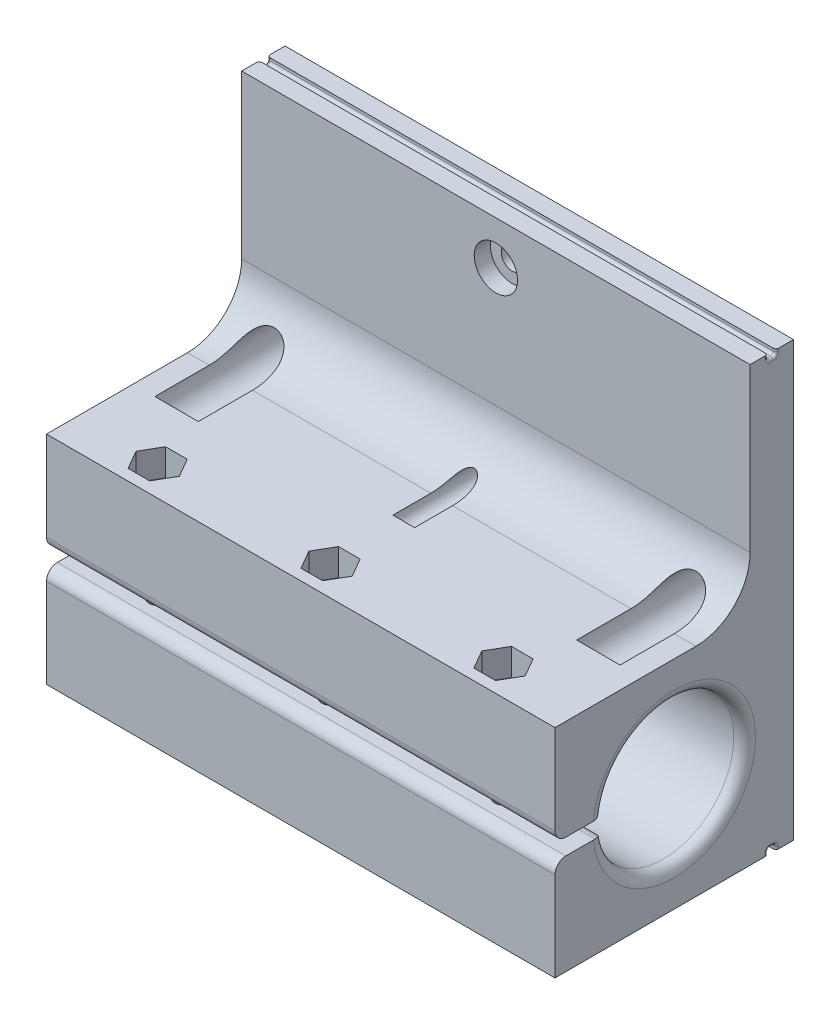
SolidWorks part; units mm, degrees
ref_plane "Front Plane" through (0, 0, 0) normal (0, 0, 1) x (1, 0, 0)
ref_plane "Top Plane" through (0, 0, 0) normal (0, 1, 0) x (1, 0, 0)
ref_plane "Right Plane" through (0, 0, 0) normal (1, 0, 0) x (0, 0, -1)
sketch "Sketch1" plane through (0, 0, 0) normal (0, 0, 1) x (1, 0, 0)
  line L1 (-46.9, -40) -> (46.9, -40)
  line L2 (-46.9, -40) -> (-46.9, 40)
  line L3 (-46.9, 40) -> (46.9, 40)
  line L4 (46.9, -40) -> (46.9, 40)
  line L5 (-46.9, -40) -> (46.9, 40) construction
  line L6 (-46.9, 40) -> (46.9, -40) construction
  point P0 (0, 0)
  dimension "D1" = 93.8
  dimension "D2" = 80
extrude "Boss-Extrude1" add sketch "Sketch1" along normal blind 8
sketch "Sketch4" plane through (0, 0, 0) normal (0, 0, -1) x (-1, 0, 0)
  circle A0 centre (0, -32) radius 2
  circle A1 centre (0, 32) radius 2
  circle A2 centre (38.9, 0) radius 2
  circle A3 centre (-38.9, 0) radius 2
extrude "Cut-Extrude2" cut sketch "Sketch4" against normal through all
sketch "Sketch5" plane through (0, 0, 0) normal (0, 0, -1) x (-1, 0, 0)
  line L1 (0, 4.001) -> (-3.465, 2.0005)
  line L2 (-3.465, 2.0005) -> (-3.465, -2.0005)
  line L3 (-3.465, -2.0005) -> (0, -4.001)
  line L4 (0, -4.001) -> (3.465, -2.0005)
  line L5 (3.465, -2.0005) -> (3.465, 2.0005)
  line L6 (3.465, 2.0005) -> (0, 4.001)
  circle A0 centre (0, 0) radius 3.465 construction
  dimension "D1" = 6.93
extrude "Cut-Extrude3" cut sketch "Sketch5" against normal blind 5
sketch "Sketch9" plane through (0, 0, 8) normal (0, 0, 1) x (1, 0, 0)
  line L0 (46.9, -40) -> (46.9, 40) construction
  line L1 (-46.9, -40) -> (46.9, -40)
  line L2 (-46.9, -40) -> (-46.9, 0)
  line L3 (-46.9, 0) -> (46.9, 0)
  line L4 (46.9, -40) -> (46.9, 0)
  dimension "D1" = 40
extrude "Boss-Extrude2" add sketch "Sketch9" along normal blind 36
sketch "Sketch8" plane through (0, 0, 8) normal (0, 0, 1) x (1, 0, 0)
  circle A0 centre (0, 32) radius 4
  circle A3 centre (-38.9, 0) radius 4
  circle A4 centre (38.9, 0) radius 4
  dimension "D1" = 8
  dimension "D2" = 8
  dimension "D3" = 8
extrude "Cut-Extrude5" cut sketch "Sketch8" against normal blind 3 and the other way blind 20
sketch "Sketch7" plane through (0, 0, 5) normal (0, 0, -1) x (-1, 0, 0)
  circle A0 centre (0, 0) radius 2
extrude "Cut-Extrude4" cut sketch "Sketch7" against normal blind 20
fillet "Fillet1" radius 10 1 edges at (-18.45, 0, 8)
sketch "Sketch10" plane through (-46.9, 0, 0) normal (-1, 0, 0) x (0, 0, 1)
  line L0 (44, -20) -> (0, -20) construction
  line L1 (44, 0) -> (44, -40) construction
  line L2 (0, 40) -> (0, -40) construction
  line L4 (34.9132, -18.5) -> (44, -18.5)
  line L6 (34.9132, -21.5) -> (44, -21.5)
  line L7 (44, -18.5) -> (44, -21.5)
  arc A0 (34.9132, -18.5) -> (34.9132, -21.5) centre (22, -20) ccw
  dimension "D2" = 26
  dimension "D1" = 22
  dimension "D3" = 1.5
  dimension "D4" = 3
extrude "Cut-Extrude6" cut sketch "Sketch10" against normal through all
fillet "Fillet2" radius 2 6 edges at (46.9, -20, 9) (-46.9, -20, 9) (0, -21.5, 44) (0, -21.5, 34.9132) (0, -18.5, 44) (0, -18.5, 34.9132)
sketch "Sketch11" plane through (0, -40, 0) normal (0, -1, 0) x (1, 0, 0)
  line L0 (-46.9, 38.5) -> (46.9, 38.5) construction
  line L1 (-46.9, 44) -> (-46.9, 0) construction
  line L2 (46.9, 44) -> (46.9, 0) construction
  line L3 (-46.9, 44) -> (46.9, 44) construction
  line L4 (0, 38.5) -> (0, 28.0799) construction
  circle A0 centre (-31.9, 38.5) radius 1.6
  circle A1 centre (0, 38.5) radius 1.6
  circle A3 centre (31.9, 38.5) radius 1.6
  dimension "D3" = 3.2
  dimension "D1" = 5.5
  dimension "D2" = 15
extrude "Cut-Extrude7" cut sketch "Sketch11" against normal through all
sketch "Sketch12" plane through (0, 0, 0) normal (0, 1, 0) x (1, 0, 0)
  line L0 (46.9, -44) -> (-46.9, -44) construction
  line L1 (-27.9047, -38.5) -> (-29.9024, -35.04)
  line L2 (-29.9024, -35.04) -> (-33.8976, -35.04)
  line L3 (-33.8976, -35.04) -> (-35.8953, -38.5)
  line L4 (-35.8953, -38.5) -> (-33.8976, -41.96)
  line L5 (-33.8976, -41.96) -> (-29.9024, -41.96)
  line L6 (-29.9024, -41.96) -> (-27.9047, -38.5)
  line L7 (3.9953, -38.5) -> (1.9976, -35.04)
  line L8 (1.9976, -35.04) -> (-1.9976, -35.04)
  line L9 (-1.9976, -35.04) -> (-3.9953, -38.5)
  line L10 (-3.9953, -38.5) -> (-1.9976, -41.96)
  line L11 (-1.9976, -41.96) -> (1.9976, -41.96)
  line L12 (1.9976, -41.96) -> (3.9953, -38.5)
  line L13 (35.8953, -38.5) -> (33.8976, -35.04)
  line L14 (33.8976, -35.04) -> (29.9024, -35.04)
  line L15 (29.9024, -35.04) -> (27.9047, -38.5)
  line L16 (27.9047, -38.5) -> (29.9024, -41.96)
  line L17 (29.9024, -41.96) -> (33.8976, -41.96)
  line L18 (33.8976, -41.96) -> (35.8953, -38.5)
  circle A0 centre (-31.9, -38.5) radius 3.46 construction
  circle A1 centre (0, -38.5) radius 3.46 construction
  circle A2 centre (31.9, -38.5) radius 3.46 construction
  dimension "D1" = 6.92
extrude "Cut-Extrude8" cut sketch "Sketch12" against normal blind 5
sketch "Sketch13" plane through (0, -40, 0) normal (0, -1, 0) x (1, 0, 0)
  circle A0 centre (-31.9, 38.5) radius 4.5
  circle A1 centre (0, 38.5) radius 4.5
  circle A2 centre (31.9, 38.5) radius 4.5
  dimension "D1" = 9
extrude "Cut-Extrude9" cut sketch "Sketch13" against normal blind 3
sketch "Sketch14" plane through (0, -40, 0) normal (0, -1, 0) x (1, 0, 0)
  line L0 (0, 0) -> (0, 29.1114) construction
  line L1 (-46.9, 0) -> (46.9, 0) construction
  line L2 (-4, 13) -> (4, 13)
  line L3 (-4, 13) -> (-4, 8)
  line L4 (-4, 8) -> (4, 8)
  line L5 (4, 13) -> (4, 8)
  dimension "D1" = 8
  dimension "D2" = 4
  dimension "D3" = 8
  dimension "D4" = 5
extrude "Cut-Extrude10" cut sketch "Sketch14" against normal blind 15
sketch "Sketch15" plane through (0, 0, 13) normal (0, 0, -1) x (-1, 0, 0)
  circle A0 centre (0, -32) radius 2
extrude "Cut-Extrude11" cut sketch "Sketch15" against normal blind 5
sketch "Sketch16" plane through (-46.9, 0, 0) normal (-1, 0, 0) x (0, 0, 1)
  line L0 (4, 40) -> (4, -40) construction
  line L1 (8, 40) -> (0, 40) construction
  line L2 (44, -40) -> (0, -40) construction
  line L3 (0, 0) -> (10.6525, 0) construction
  line L4 (4.75, -40) -> (4.75, -39)
  line L5 (3.25, 40) -> (4.75, 40)
  line L6 (3.25, 40) -> (3.25, 39)
  line L7 (3.25, 39) -> (4.75, 39)
  line L8 (4.75, 40) -> (4.75, 39)
  line L9 (3.25, -39) -> (4.75, -39)
  line L10 (3.25, -40) -> (3.25, -39)
  line L11 (3.25, -40) -> (4.75, -40)
  dimension "D1" = 1.5
  dimension "D2" = 1
  dimension "D3" = 0.75
extrude "Cut-Extrude12" cut sketch "Sketch16" against normal through all
fillet "Fillet3" radius 0.5 16 edges at (46.9, -39.5, 4.75) (46.9, -39.5, 3.25) (-46.9, -39.5, 3.25) (-46.9, -39.5, 4.75) (46.9, 39.5, 3.25) (46.9, 39.5, 4.75) (-46.9, 39.5, 4.75) (-46.9, 39.5, 3.25) (46.9, -39, 4) (0, -39, 3.25) (-46.9, -39, 4) (0, -39, 4.75) (46.9, 39, 4) (0, 39, 4.75) (-46.9, 39, 4) (0, 39, 3.25)
